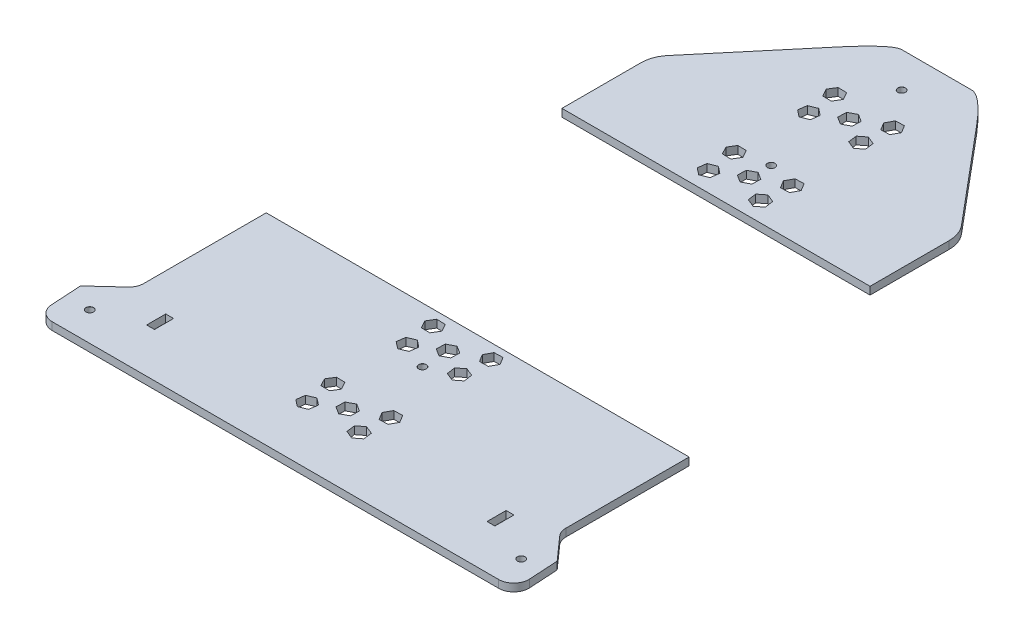
SolidWorks part; units mm, degrees
ref_plane "Front Plane" through (0, 0, 0) normal (0, 0, 1) x (1, 0, 0)
ref_plane "Top Plane" through (0, 0, 0) normal (0, 1, 0) x (1, 0, 0)
ref_plane "Right Plane" through (0, 0, 0) normal (1, 0, 0) x (0, 0, -1)
sketch "Sketch1" plane through (0, 0, 0) normal (0, 1, 0) x (1, 0, 0)
  line L0 (0, 135) -> (0, -128.25) construction
  line L1 (-100, 135) -> (100, 135)
  line L2 (-100, 135) -> (-100, -28.4287)
  line L3 (-95, -128.25) -> (95, -128.25)
  line L4 (100, 135) -> (100, -28.4287)
  line L5 (-100, 135) -> (95, -128.25) construction
  line L6 (-95, -128.25) -> (100, 135) construction
  line L7 (-17.7045, 135) -> (-58.6066, 86.2548)
  line L8 (-61.4141, 78.5413) -> (-61.4141, 44.5413)
  line L9 (-65.8622, 35.2156) -> (-100, 7.5713)
  line L10 (-100, -28.4287) -> (-84.294, -31.4816)
  line L11 (-84.294, -31.4816) -> (-84.294, -99.4131)
  line L12 (-84.294, -99.4131) -> (-96.0652, -110.25)
  line L13 (93.9348, -110.25) -> (95, -128.25)
  line L14 (84.294, -99.4131) -> (93.9348, -110.25)
  line L15 (100, -28.4287) -> (84.294, -31.4816)
  line L16 (84.294, -31.4816) -> (84.294, -99.4131)
  line L17 (17.7045, 135) -> (58.6066, 86.2548)
  line L18 (61.4141, 78.5413) -> (61.4141, 44.5413)
  line L19 (65.8622, 35.2156) -> (100, 7.5713)
  line L20 (-96.0652, -110.25) -> (-95, -128.25)
  arc A0 (-58.6066, 86.2548) -> (-61.4141, 78.5413) centre (-49.4141, 78.5413) ccw
  arc A1 (-61.4141, 44.5413) -> (-65.8622, 35.2156) centre (-73.4141, 44.5413) cw
  arc A2 (61.4141, 44.5413) -> (65.8622, 35.2156) centre (73.4141, 44.5413) ccw
  arc A3 (58.6066, 86.2548) -> (61.4141, 78.5413) centre (49.4141, 78.5413) cw
  point P0 (0, 0)
  point P14 (-61.4141, 82.909)
  dimension "D6" = 12
  dimension "D1" = 200
  dimension "D2" = 190
  dimension "D3" = 50
  dimension "D4" = 68
  dimension "D5" = 51
  dimension "D7" = 16
  dimension "D8" = 79
  dimension "D9" = 18
  dimension "D10" = 34
  dimension "D11" = 36
  dimension "D12" = 163.4287
extrude "Boss-Extrude1" add sketch "Sketch1" along normal blind 3.06 contours A3 L17 L1 L7 A0 L8 A1 L9 L2 L10 L11 L12 L3 L4 L14 L16 L15 L19 A2 L18 region at (-0.0735, 0, 14.9011)
fillet "Fillet1" radius 6 10 edges at (100, 1.53, 28.4287) (-100, 1.53, 28.4287) (-100, 1.53, -7.5713) (100, 1.53, -7.5713) (-95, 1.53, 128.25) (95, 1.53, 128.25) (84.294, 1.53, 99.4131) (84.294, 1.53, 31.4816) (-84.294, 1.53, 31.4816) (-84.294, 1.53, 99.4131)
fillet "Fillet2" radius 17 1 edges at (-17.7045, 1.53, -135) second distance 22 first distance on face at (0, 1.53, -135)
fillet "Fillet3" radius 22 1 edges at (17.7045, 1.53, -135) second distance 17 first distance on face at (38.1555, 1.53, -110.6274)
sketch "Sketch3" plane through (0, 3.06, 0) normal (0, 1, 0) x (1, 0, 0)
  line L8 (-0.3551, 135) -> (-0.3551, -128.25) construction
  line L10 (-89.3446, -128.25) -> (88.6344, -128.25) construction
  line L11 (-26.9955, 123.9274) -> (-58.6066, 86.2548) construction
  line L12 (-13.7043, 103.2521) -> (-10.2412, 103.1718)
  line L13 (-10.2412, 103.1718) -> (-8.44, 106.1308)
  line L14 (-8.44, 106.1308) -> (-10.102, 109.1702)
  line L15 (-10.102, 109.1702) -> (-13.5652, 109.2505)
  line L16 (-13.5652, 109.2505) -> (-15.3663, 106.2915)
  line L17 (-15.3663, 106.2915) -> (-13.7043, 103.2521)
  line L18 (-11.1921, 91.3091) -> (-7.9828, 92.613)
  line L19 (-7.9828, 92.613) -> (-7.5073, 96.0443)
  line L20 (-7.5073, 96.0443) -> (-10.2412, 98.1718)
  line L21 (-10.2412, 98.1718) -> (-13.4505, 96.8679)
  line L22 (-13.4505, 96.8679) -> (-13.926, 93.4366)
  line L23 (-13.926, 93.4366) -> (-11.1921, 91.3091)
  line L24 (2.5753, 98.6911) -> (2.7101, 102.1525)
  line L25 (2.7101, 102.1525) -> (-0.2203, 104)
  line L26 (-0.2203, 104) -> (-3.2854, 102.386)
  line L27 (-3.2854, 102.386) -> (-3.4202, 98.9245)
  line L28 (-3.4202, 98.9245) -> (-0.4898, 97.077)
  line L29 (-0.4898, 97.077) -> (2.5753, 98.6911)
  line L30 (26.9955, 123.9274) -> (58.6066, 86.2548) construction
  line L31 (13.2159, 93.4366) -> (10.482, 91.3091)
  line L32 (12.7404, 96.8679) -> (13.2159, 93.4366)
  line L33 (9.531, 98.1718) -> (12.7404, 96.8679)
  line L34 (6.7972, 96.0443) -> (9.531, 98.1718)
  line L35 (7.2727, 92.613) -> (6.7972, 96.0443)
  line L36 (10.482, 91.3091) -> (7.2727, 92.613)
  line L37 (14.6562, 106.2915) -> (12.9942, 103.2521)
  line L38 (12.8551, 109.2505) -> (14.6562, 106.2915)
  line L39 (9.3919, 109.1702) -> (12.8551, 109.2505)
  line L40 (7.7299, 106.1308) -> (9.3919, 109.1702)
  line L41 (9.531, 103.1718) -> (7.7299, 106.1308)
  line L42 (12.9942, 103.2521) -> (9.531, 103.1718)
  line L49 (13.2159, 53.4366) -> (10.482, 51.3091)
  line L50 (10.482, 51.3091) -> (7.2727, 52.613)
  line L51 (7.2727, 52.613) -> (6.7972, 56.0443)
  line L52 (6.7972, 56.0443) -> (9.531, 58.1718)
  line L53 (9.531, 58.1718) -> (12.7404, 56.8679)
  line L54 (12.7404, 56.8679) -> (13.2159, 53.4366)
  line L55 (-0.4898, 57.077) -> (2.5753, 58.6911)
  line L56 (-3.4202, 58.9245) -> (-0.4898, 57.077)
  line L57 (-3.2854, 62.386) -> (-3.4202, 58.9245)
  line L58 (-0.2203, 64) -> (-3.2854, 62.386)
  line L59 (2.7101, 62.1525) -> (-0.2203, 64)
  line L60 (2.5753, 58.6911) -> (2.7101, 62.1525)
  line L61 (-7.9828, 52.613) -> (-7.5073, 56.0443)
  line L62 (-11.1921, 51.3091) -> (-7.9828, 52.613)
  line L63 (-13.926, 53.4366) -> (-11.1921, 51.3091)
  line L64 (-13.4505, 56.8679) -> (-13.926, 53.4366)
  line L65 (-10.2412, 58.1718) -> (-13.4505, 56.8679)
  line L66 (-7.5073, 56.0443) -> (-10.2412, 58.1718)
  line L67 (-10.2412, 63.1718) -> (-8.44, 66.1308)
  line L68 (-13.7043, 63.2521) -> (-10.2412, 63.1718)
  line L69 (-15.3663, 66.2915) -> (-13.7043, 63.2521)
  line L70 (-13.5652, 69.2505) -> (-15.3663, 66.2915)
  line L71 (-10.102, 69.1702) -> (-13.5652, 69.2505)
  line L72 (-8.44, 66.1308) -> (-10.102, 69.1702)
  line L73 (9.3919, 69.1702) -> (12.8551, 69.2505)
  line L74 (12.8551, 69.2505) -> (14.6562, 66.2915)
  line L75 (14.6562, 66.2915) -> (12.9942, 63.2521)
  line L76 (12.9942, 63.2521) -> (9.531, 63.1718)
  line L77 (9.531, 63.1718) -> (7.7299, 66.1308)
  line L78 (7.7299, 66.1308) -> (9.3919, 69.1702)
  line L79 (13.2159, 13.4366) -> (10.482, 11.3091)
  line L80 (10.482, 11.3091) -> (7.2727, 12.613)
  line L81 (7.2727, 12.613) -> (6.7972, 16.0443)
  line L82 (6.7972, 16.0443) -> (9.531, 18.1718)
  line L83 (9.531, 18.1718) -> (12.7404, 16.8679)
  line L84 (12.7404, 16.8679) -> (13.2159, 13.4366)
  line L85 (-0.4898, 17.077) -> (2.5753, 18.6911)
  line L86 (-3.4202, 18.9245) -> (-0.4898, 17.077)
  line L87 (-3.2854, 22.386) -> (-3.4202, 18.9245)
  line L88 (-0.2203, 24) -> (-3.2854, 22.386)
  line L89 (2.7101, 22.1525) -> (-0.2203, 24)
  line L90 (2.5753, 18.6911) -> (2.7101, 22.1525)
  line L91 (-7.9828, 12.613) -> (-7.5073, 16.0443)
  line L92 (-11.1921, 11.3091) -> (-7.9828, 12.613)
  line L93 (-13.926, 13.4366) -> (-11.1921, 11.3091)
  line L94 (-13.4505, 16.8679) -> (-13.926, 13.4366)
  line L95 (-10.2412, 18.1718) -> (-13.4505, 16.8679)
  line L96 (-7.5073, 16.0443) -> (-10.2412, 18.1718)
  line L97 (-10.2412, 23.1718) -> (-8.44, 26.1308)
  line L98 (-13.7043, 23.2521) -> (-10.2412, 23.1718)
  line L99 (-15.3663, 26.2915) -> (-13.7043, 23.2521)
  line L100 (-13.5652, 29.2505) -> (-15.3663, 26.2915)
  line L101 (-10.102, 29.1702) -> (-13.5652, 29.2505)
  line L102 (-8.44, 26.1308) -> (-10.102, 29.1702)
  line L103 (9.3919, 29.1702) -> (12.8551, 29.2505)
  line L104 (12.8551, 29.2505) -> (14.6562, 26.2915)
  line L105 (14.6562, 26.2915) -> (12.9942, 23.2521)
  line L106 (12.9942, 23.2521) -> (9.531, 23.1718)
  line L107 (9.531, 23.1718) -> (7.7299, 26.1308)
  line L108 (7.7299, 26.1308) -> (9.3919, 29.1702)
  line L109 (13.2159, -26.5634) -> (10.482, -28.6909)
  line L110 (10.482, -28.6909) -> (7.2727, -27.387)
  line L111 (7.2727, -27.387) -> (6.7972, -23.9557)
  line L112 (6.7972, -23.9557) -> (9.531, -21.8282)
  line L113 (9.531, -21.8282) -> (12.7404, -23.1321)
  line L114 (12.7404, -23.1321) -> (13.2159, -26.5634)
  line L115 (-0.4898, -22.923) -> (2.5753, -21.3089)
  line L116 (-3.4202, -21.0755) -> (-0.4898, -22.923)
  line L117 (-3.2854, -17.614) -> (-3.4202, -21.0755)
  line L118 (-0.2203, -16) -> (-3.2854, -17.614)
  line L119 (2.7101, -17.8475) -> (-0.2203, -16)
  line L120 (2.5753, -21.3089) -> (2.7101, -17.8475)
  line L121 (-7.9828, -27.387) -> (-7.5073, -23.9557)
  line L122 (-11.1921, -28.6909) -> (-7.9828, -27.387)
  line L123 (-13.926, -26.5634) -> (-11.1921, -28.6909)
  line L124 (-13.4505, -23.1321) -> (-13.926, -26.5634)
  line L125 (-10.2412, -21.8282) -> (-13.4505, -23.1321)
  line L126 (-7.5073, -23.9557) -> (-10.2412, -21.8282)
  line L127 (-10.2412, -16.8282) -> (-8.44, -13.8692)
  line L128 (-13.7043, -16.7479) -> (-10.2412, -16.8282)
  line L129 (-15.3663, -13.7085) -> (-13.7043, -16.7479)
  line L130 (-13.5652, -10.7495) -> (-15.3663, -13.7085)
  line L131 (-10.102, -10.8298) -> (-13.5652, -10.7495)
  line L132 (-8.44, -13.8692) -> (-10.102, -10.8298)
  line L133 (9.3919, -10.8298) -> (12.8551, -10.7495)
  line L134 (12.8551, -10.7495) -> (14.6562, -13.7085)
  line L135 (14.6562, -13.7085) -> (12.9942, -16.7479)
  line L136 (12.9942, -16.7479) -> (9.531, -16.8282)
  line L137 (9.531, -16.8282) -> (7.7299, -13.8692)
  line L138 (7.7299, -13.8692) -> (9.3919, -10.8298)
  line L139 (13.2159, -66.5634) -> (10.482, -68.6909)
  line L140 (10.482, -68.6909) -> (7.2727, -67.387)
  line L141 (7.2727, -67.387) -> (6.7972, -63.9557)
  line L142 (6.7972, -63.9557) -> (9.531, -61.8282)
  line L143 (9.531, -61.8282) -> (12.7404, -63.1321)
  line L144 (12.7404, -63.1321) -> (13.2159, -66.5634)
  line L145 (-0.4898, -62.923) -> (2.5753, -61.3089)
  line L146 (-3.4202, -61.0755) -> (-0.4898, -62.923)
  line L147 (-3.2854, -57.614) -> (-3.4202, -61.0755)
  line L148 (-0.2203, -56) -> (-3.2854, -57.614)
  line L149 (2.7101, -57.8475) -> (-0.2203, -56)
  line L150 (2.5753, -61.3089) -> (2.7101, -57.8475)
  line L151 (-7.9828, -67.387) -> (-7.5073, -63.9557)
  line L152 (-11.1921, -68.6909) -> (-7.9828, -67.387)
  line L153 (-13.926, -66.5634) -> (-11.1921, -68.6909)
  line L154 (-13.4505, -63.1321) -> (-13.926, -66.5634)
  line L155 (-10.2412, -61.8282) -> (-13.4505, -63.1321)
  line L156 (-7.5073, -63.9557) -> (-10.2412, -61.8282)
  line L157 (-10.2412, -56.8282) -> (-8.44, -53.8692)
  line L158 (-13.7043, -56.7479) -> (-10.2412, -56.8282)
  line L159 (-15.3663, -53.7085) -> (-13.7043, -56.7479)
  line L160 (-13.5652, -50.7495) -> (-15.3663, -53.7085)
  line L161 (-10.102, -50.8298) -> (-13.5652, -50.7495)
  line L162 (-8.44, -53.8692) -> (-10.102, -50.8298)
  line L163 (9.3919, -50.8298) -> (12.8551, -50.7495)
  line L164 (12.8551, -50.7495) -> (14.6562, -53.7085)
  line L165 (14.6562, -53.7085) -> (12.9942, -56.7479)
  line L166 (12.9942, -56.7479) -> (9.531, -56.8282)
  line L167 (9.531, -56.8282) -> (7.7299, -53.8692)
  line L168 (7.7299, -53.8692) -> (9.3919, -50.8298)
  line L169 (13.2159, -106.5634) -> (10.482, -108.6909)
  line L170 (10.482, -108.6909) -> (7.2727, -107.387)
  line L171 (7.2727, -107.387) -> (6.7972, -103.9557)
  line L172 (6.7972, -103.9557) -> (9.531, -101.8282)
  line L173 (9.531, -101.8282) -> (12.7404, -103.1321)
  line L174 (12.7404, -103.1321) -> (13.2159, -106.5634)
  line L175 (-0.4898, -102.923) -> (2.5753, -101.3089)
  line L176 (-3.4202, -101.0755) -> (-0.4898, -102.923)
  line L177 (-3.2854, -97.614) -> (-3.4202, -101.0755)
  line L178 (-0.2203, -96) -> (-3.2854, -97.614)
  line L179 (2.7101, -97.8475) -> (-0.2203, -96)
  line L180 (2.5753, -101.3089) -> (2.7101, -97.8475)
  line L181 (-7.9828, -107.387) -> (-7.5073, -103.9557)
  line L182 (-11.1921, -108.6909) -> (-7.9828, -107.387)
  line L183 (-13.926, -106.5634) -> (-11.1921, -108.6909)
  line L184 (-13.4505, -103.1321) -> (-13.926, -106.5634)
  line L185 (-10.2412, -101.8282) -> (-13.4505, -103.1321)
  line L186 (-7.5073, -103.9557) -> (-10.2412, -101.8282)
  line L187 (-10.2412, -96.8282) -> (-8.44, -93.8692)
  line L188 (-13.7043, -96.7479) -> (-10.2412, -96.8282)
  line L189 (-15.3663, -93.7085) -> (-13.7043, -96.7479)
  line L190 (-13.5652, -90.7495) -> (-15.3663, -93.7085)
  line L191 (-10.102, -90.8298) -> (-13.5652, -90.7495)
  line L192 (-8.44, -93.8692) -> (-10.102, -90.8298)
  line L193 (9.3919, -90.8298) -> (12.8551, -90.7495)
  line L194 (12.8551, -90.7495) -> (14.6562, -93.7085)
  line L195 (14.6562, -93.7085) -> (12.9942, -96.7479)
  line L196 (12.9942, -96.7479) -> (9.531, -96.8282)
  line L197 (9.531, -96.8282) -> (7.7299, -93.8692)
  line L198 (7.7299, -93.8692) -> (9.3919, -90.8298)
  circle A2 centre (-11.9032, 106.2111) radius 3 construction
  circle A3 centre (-10.7166, 94.7405) radius 3 construction
  circle A4 centre (-0.3551, 100.5385) radius 3 construction
  circle A5 centre (10.0065, 94.7405) radius 3 construction
  circle A6 centre (11.1931, 106.2111) radius 3 construction
  point P22 (-9.3406, 104.6513)
  dimension "D9" = 6
  dimension "D12" = 6
  dimension "D13" = 5
  dimension "D14" = 6
  dimension "D15" = 7
  dimension "D16" = 5
  dimension "D17" = 32.11
  dimension "D18" = 42.23
  dimension "D19" = 31
  dimension "D20" = 26.0489
  dimension "D21" = 6
extrude "Cut-Extrude1" cut sketch "Sketch3" against normal blind 5 contours L54 L53 L52 L51 L50 L49 | L78 L77 L76 L75 L74 L73 | L61 L66 L65 L64 L63 L62 | L97 L102 L101 L100 L99 L98 | L85 L90 L89 L88 L87 L86 | L121 L126 L125 L124 L123 L122 | L168 L167 L166 L165 L164 L163 | L145 L150 L149 L148 L147 L146 | L151 L156 L155 L154 L153 L152 | L157 L162 L161 L160 L159 L158 | L198 L197 L196 L195 L194 L193 | L174 L173 L172 L171 L170 L169 | L175 L180 L179 L178 L177 L176 | L181 L186 L185 L184 L183 L182 | L187 L192 L191 L190 L189 L188 | L42 L37 L38 L39 L40 L41 | L36 L31 L32 L33 L34 L35 | L22 L23 L18 L19 L20 L21 | L28 L29 L24 L25 L26 L27 | L16 L17 L12 L13 L14 L15 | L60 L59 L58 L57 L56 L55 | L67 L72 L71 L70 L69 L68 | L104 L105 L106 L107 L108 L103 | L79 L80 L81 L82 L83 L84 | L96 L95 L94 L93 L92 L91 | L137 L138 L133 L134 L135 L136 | L112 L113 L114 L109 L110 L111 | L120 L119 L118 L117 L116 L115 | L132 L131 L130 L129 L128 L127 | L144 L139 L140 L141 L142 L143 region at (-11.9032, 3.06, -106.2111) region at (-10.7166, 3.06, -94.7405) region at (-0.3551, 3.06, -100.5385) region at (10.0065, 3.06, -94.7405) region at (11.1931, 3.06, -106.2111) region at (10.0065, 3.06, -54.7405) region at (-10.7166, 3.06, -54.7405) region at (11.1931, 3.06, -66.2111) region at (-0.3551, 3.06, -20.5385) region at (-11.9032, 3.06, -26.2111) region at (-10.7166, 3.06, 25.2595) region at (-0.3551, 3.06, 59.4615) region at (-10.7166, 3.06, 65.2595) region at (-11.9032, 3.06, 53.7889) region at (11.1931, 3.06, 53.7889) region at (10.0065, 3.06, 105.2595) region at (-0.3551, 3.06, 99.4615) region at (-10.7166, 3.06, 105.2595) region at (-11.9032, 3.06, 93.7889) region at (11.1931, 3.06, 93.7889)
sketch "Sketch6" plane through (0, 3.06, 0) normal (0, 1, 0) x (1, 0, 0)
  line L0 (-13.9728, 135) -> (13.9728, 135) construction
  line L1 (-100, -48) -> (100, -48)
  line L2 (-100, -48) -> (-100, 47)
  line L3 (-100, 47) -> (100, 47)
  line L4 (100, -48) -> (100, 47)
  line L5 (-100, 4.7095) -> (-100, -23.4826) construction
  line L6 (100, 4.7095) -> (100, -23.4826) construction
  dimension "D1" = 95
  dimension "D2" = 88
extrude "Cut-Extrude3" cut sketch "Sketch6" against normal blind 5
hole_wizard "Ø2.0mm Dowel Hole1" positions "Sketch7" profile "Sketch8" hole size "Ø3.0" standard "ISO" end condition through all
sketch "Sketch7" plane through (0, 3.06, 0) normal (0, 1, 0) x (1, 0, 0)
  circle A0 centre (86, -116.6542) radius 1 construction
  circle A1 centre (-86, -116.6542) radius 1 construction
  circle A2 centre (0, 121) radius 1 construction
  point P0 (0, 121)
  point P3 (86, -116.6542)
  point P5 (-86, -116.6542)
sketch "Sketch8" plane through (0, 3.06, -121) normal (1, 0, 0) x (0, 0, 1)
  line L0 (0, 0) -> (0, 3.17)
  line L1 (0, 3.17) -> (1.5, 3.17)
  line L2 (1.5, 3.17) -> (1.5, 0.025)
  line L3 (1.5, 0.025) -> (1.525, 0)
  line L5 (1.525, 0) -> (0, 0)
  line L6 (-1.5, 0.025) -> (-1.525, 0) construction
  line L11 (0, -6.35) -> (0, 107.95) construction
  dimension "Thru Hole Dia." = 3
  dimension "Thru Hole Depth" = 3.17
  dimension "Near C'Sink Dia." = 3.05
  dimension "Near C'Sink Angle" = 90
sketch "Sketch9" plane through (0, 0, 0) normal (0, -1, 0) x (1, 0, 0)
  line L16 (-70, 135) -> (70, 135) construction
  line L20 (-69.4034, 110.56) -> (-69.4034, 102.94)
  line L21 (-69.4034, 102.94) -> (-66.2834, 102.94)
  line L22 (-66.2834, 102.94) -> (-66.2834, 110.56)
  line L23 (-66.2834, 110.56) -> (-69.4034, 110.56)
  dimension "D1" = 3.12
  dimension "D2" = 7.62
  dimension "D3" = 14.8906
  dimension "D4" = 24.44
extrude "Cut-Extrude5" cut sketch "Sketch9" against normal up to surface (3.06 mm away) up to face at (86, 3.06, 118.1792)
mirror "Mirror1" about plane through (0, 0, 0) normal (1, 0, 0) of "Cut-Extrude5"
sketch "Sketch10" plane through (0, 3.06, 0) normal (0, 1, 0) x (1, 0, 0)
  line L0 (-84.294, -48) -> (84.294, -48) construction
  line L1 (61.4141, 47) -> (-61.4141, 47) construction
  point P0 (0, -70)
  point P5 (0, 69)
  dimension "D1" = 22
  dimension "D2" = 22
hole_wizard "Ø3.0mm Dowel Hole1" positions "Sketch10" profile "Sketch11" hole size "Ø3.0" standard "ISO" end condition through all
sketch "Sketch11" plane through (0, 3.06, 70) normal (1, 0, 0) x (0, 0, 1)
  line L0 (0, 0) -> (0, 3.17)
  line L1 (0, 3.17) -> (1.5, 3.17)
  line L2 (1.5, 3.17) -> (1.5, 0.025)
  line L3 (1.5, 0.025) -> (1.525, 0)
  line L5 (1.525, 0) -> (0, 0)
  line L6 (-1.5, 0.025) -> (-1.525, 0) construction
  line L11 (0, -6.35) -> (0, 107.95) construction
  dimension "Thru Hole Dia." = 3
  dimension "Thru Hole Depth" = 3.17
  dimension "Near C'Sink Dia." = 3.05
  dimension "Near C'Sink Angle" = 90
